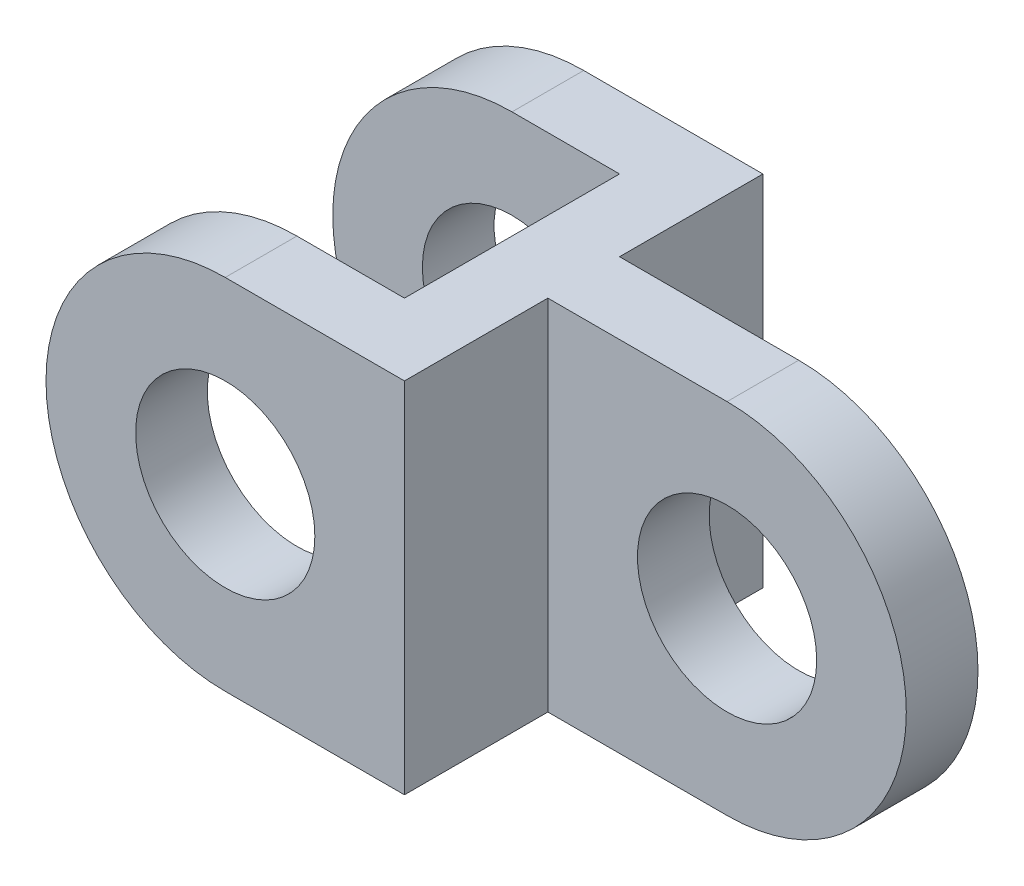
SolidWorks part; units mm, degrees
ref_plane "Alzado" through (0, 0, 0) normal (0, 0, 1) x (1, 0, 0)
ref_plane "Planta" through (0, 0, 0) normal (0, 1, 0) x (1, 0, 0)
ref_plane "Vista lateral" through (0, 0, 0) normal (1, 0, 0) x (0, 0, -1)
sketch "Croquis1" plane through (0, 0, 0) normal (0, 1, 0) x (1, 0, 0)
  line L0 (-100, 100) -> (0, 100)
  line L1 (0, 100) -> (0, 0)
  line L2 (0, 0) -> (-100, 0)
  line L3 (-100, 0) -> (-100, 20)
  line L4 (-100, 20) -> (-20, 20)
  line L5 (-20, 20) -> (-20, 80)
  line L6 (-100, 100) -> (-100, 80)
  line L7 (-100, 80) -> (-20, 80)
  point P2 (0, 0)
  point P8 (0, 0)
  point P10 (-34.4312, 20.8434)
  point P11 (0, 0)
  point P12 (0, 0)
  point P13 (0, 0)
  point P14 (0, 0)
  point P15 (0, 0)
  dimension "D1" = 100
  dimension "D2" = 100
  dimension "D3" = 100
  dimension "D4" = 60
  dimension "D5" = 20
  dimension "D6" = 20
  dimension "D7" = 20
  dimension "D8" = 80
extrude "Saliente-Extruir1" add sketch "Croquis1" along normal blind 100
fillet "Redondeo1" 2 edges at (-100, 100, -90) (-100, 0, -90) type full round first side face at (-55, 100, -50) second side face at (-55, 0, -50) middle face at (-100, 50, -90)
fillet "Redondeo2" 2 edges at (-100, 0, -10) (-100, 100, -10) type full round first side face at (-42.5, 0, -50) second side face at (-42.5, 100, -50) middle face at (-100, 50, -10)
sketch "Croquis3" plane through (0, 0, 0) normal (0, 0, 1) x (1, 0, 0)
  circle A1 centre (-50, 50) radius 25
  dimension "D1" = 50
extrude "Cortar-Extruir1" cut sketch "Croquis3" against normal through all
sketch "Croquis10" plane through (0, 0, 0) normal (1, 0, 0) x (0, 0, -1)
  line L0 (0, 100) -> (100, 100) construction
  line L6 (0, 100) -> (40, 100)
  line L7 (100, 100) -> (60, 100)
  line L8 (100, 100) -> (100, 0) construction
  line L9 (0, 0) -> (100, 0) construction
  line L10 (40, 100) -> (60, 100)
  line L11 (40, 100) -> (40, 0)
  line L12 (40, 0) -> (60, 0)
  line L13 (60, 100) -> (60, 0)
  point P8 (50, 100)
  line M5 (0, 0) -> (100, 0)
  line M7 (100, 100) -> (0, 100)
  dimension "D1" = 40
  dimension "D2" = 40
  dimension "D3" = 20
  dimension "D4" = 100
extrude "Saliente-Extruir3" add sketch "Croquis10" along normal blind 100 contours L13 L11 M7 M5 region at (0, 50, -50)
fillet "Redondeo3" 2 edges at (100, 100, -50) (100, 0, -50) type full round first side face at (-3.3333, 100, -50) second side face at (-3.3333, 0, -50) middle face at (100, 50, -50)
sketch "Croquis11" plane through (0, 0, -40) normal (0, 0, 1) x (1, 0, 0)
  line L1 (0, 100) -> (0, 0) construction
  circle A0 centre (50, 50) radius 25
  point P2 (0, 0)
  point P3 (0, 0)
  point P7 (0, 50)
  point P8 (50, 100)
  dimension "D1" = 50
  dimension "D2" = 50
extrude "Cortar-Extruir5" cut sketch "Croquis11" against normal through all
